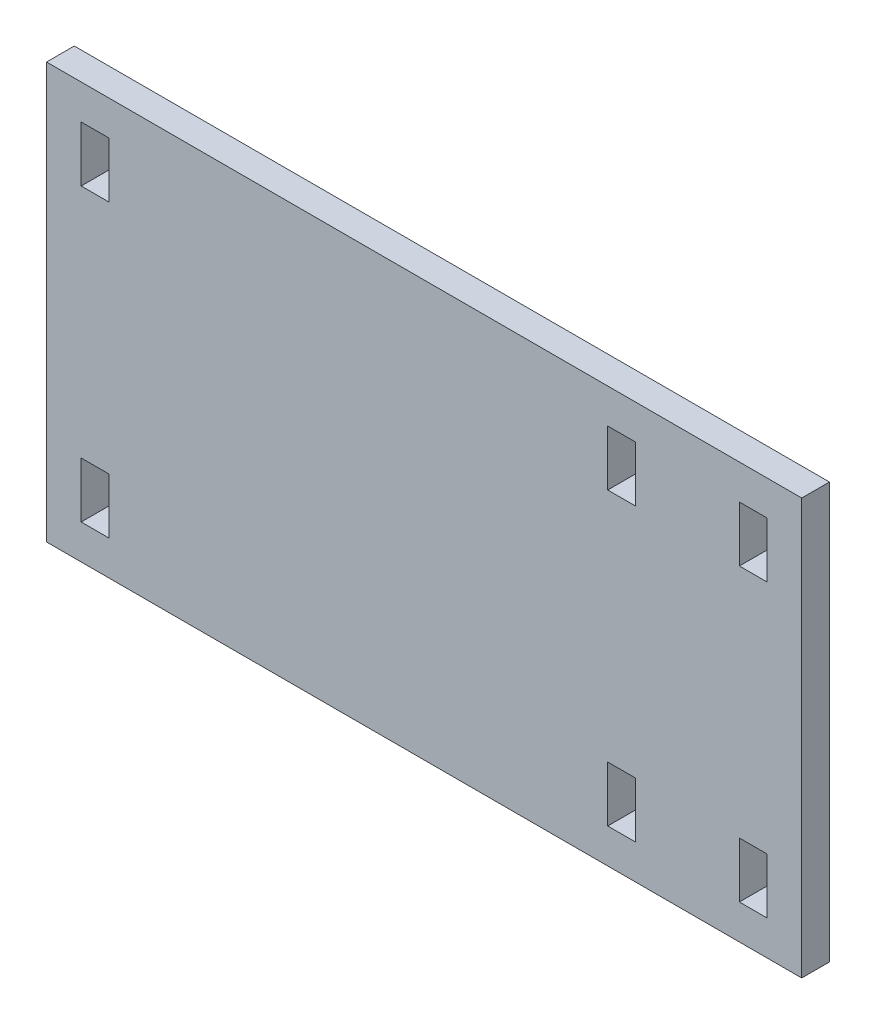
SolidWorks part; units mm, degrees
ref_plane "Front Plane" through (0, 0, 0) normal (0, 0, 1) x (1, 0, 0)
ref_plane "Top Plane" through (0, 0, 0) normal (0, 1, 0) x (1, 0, 0)
ref_plane "Right Plane" through (0, 0, 0) normal (1, 0, 0) x (0, 0, -1)
sketch "Sketch1" plane through (0, 0, 0) normal (0, 0, 1) x (1, 0, 0)
  line L0 (0, 66.0849) -> (0, -70.4198) construction
  line L1 (-45, -30) -> (55, -30)
  line L3 (-45, 30) -> (55, 30)
  line L7 (36, 25) -> (40, 25)
  line L8 (36, 25) -> (36, 17)
  line L9 (36, 17) -> (40, 17)
  line L10 (40, 25) -> (40, 17)
  line L11 (-103.5149, 0) -> (102.2922, 0) construction
  line L12 (36, -17) -> (40, -17)
  line L13 (36, -25) -> (36, -17)
  line L14 (40, -25) -> (40, -17)
  line L15 (36, -25) -> (40, -25)
  line L16 (-36, 25) -> (-40, 25)
  line L17 (-36, 25) -> (-36, 17)
  line L18 (-40, 25) -> (-40, 17)
  line L19 (-36, 17) -> (-40, 17)
  line L20 (-36, -17) -> (-40, -17)
  line L21 (-36, -25) -> (-36, -17)
  line L22 (-40, -25) -> (-40, -17)
  line L23 (-36, -25) -> (-40, -25)
  line L27 (55, 30) -> (64, 30)
  line L36 (64, 30) -> (64, -30)
  line L37 (64, -30) -> (55, -30)
  line L38 (-45, -30) -> (-45, 30)
  line L39 (55, 25) -> (59, 25)
  line L40 (55, 25) -> (55, 17)
  line L41 (55, 17) -> (59, 17)
  line L42 (59, 25) -> (59, 17)
  line L43 (55, -17) -> (59, -17)
  line L44 (55, -17) -> (55, -25)
  line L45 (55, -25) -> (59, -25)
  line L46 (59, -17) -> (59, -25)
  point P0 (0, 0)
  dimension "D1" = 60
  dimension "D2" = 15
  dimension "D4" = 5
  dimension "D5" = 4
  dimension "D6" = 8
  dimension "D7" = 72
  dimension "D9" = 15
  dimension "D10" = 5
  dimension "D11" = 5
extrude "Boss-Extrude1" add sketch "Sketch1" along normal blind 4
